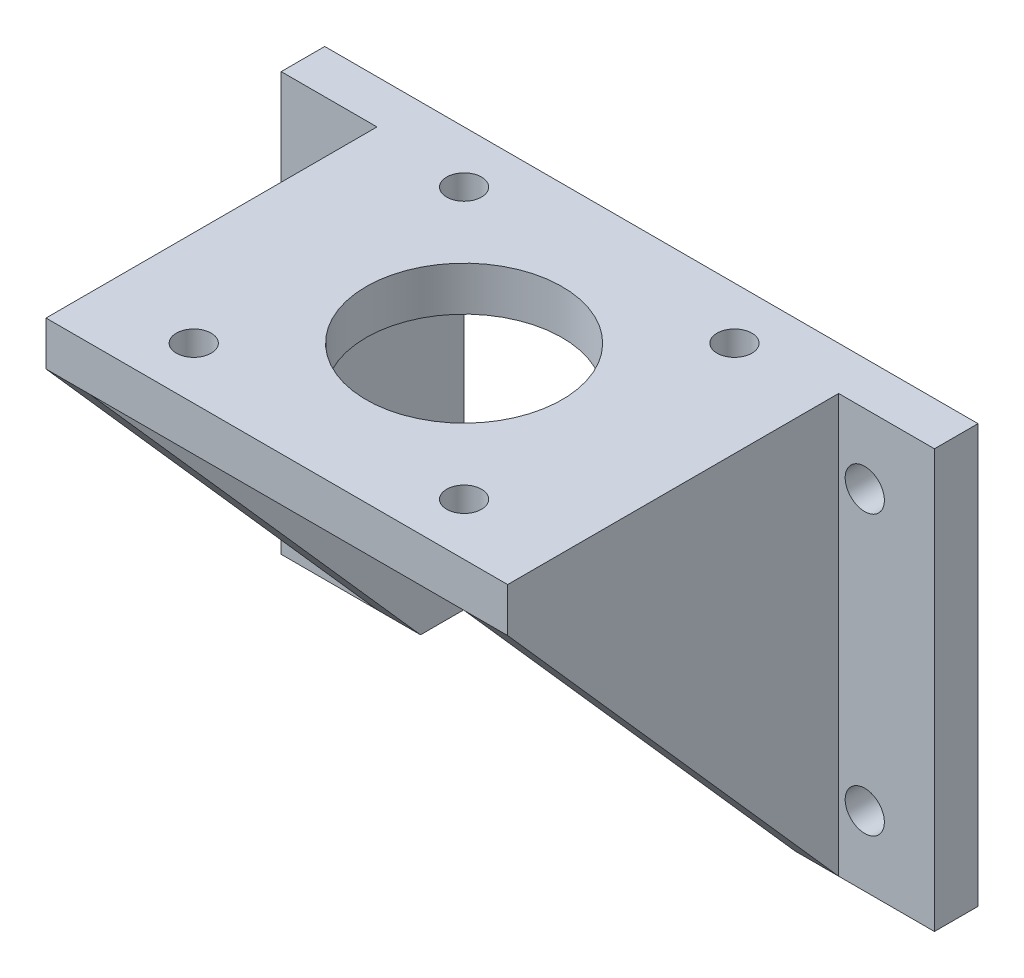
SolidWorks part; units mm, degrees
material "Copper"
ref_plane "Front Plane" through (0, 0, 0) normal (0, 0, 1) x (1, 0, 0)
ref_plane "Top Plane" through (0, 0, 0) normal (0, 1, 0) x (1, 0, 0)
ref_plane "Right Plane" through (0, 0, 0) normal (1, 0, 0) x (0, 0, -1)
sketch "Sketch1" plane through (0, 0, 0) normal (0, 0, 1) x (1, 0, 0)
  line L0 (0, 0) -> (0, 43)
  line L1 (0, 43) -> (43, 43)
  line L2 (43, 43) -> (43, 0)
  line L3 (43, 0) -> (59, 0)
  line L4 (59, 0) -> (59, 48)
  line L5 (59, 48) -> (-16, 48)
  line L6 (-16, 48) -> (-16, 0)
  line L7 (-16, 0) -> (0, 0)
  circle A0 centre (-8, 40) radius 2.25
  circle A1 centre (51, 40) radius 2.25
  circle A2 centre (51, 8) radius 2.25
  circle A3 centre (-8, 8) radius 2.25
  dimension "D5" = 8
  dimension "D1" = 16
  dimension "D2" = 16
  dimension "D3" = 5
  dimension "D4" = 43
  dimension "D6" = 8
  dimension "D7" = 2
  dimension "D8" = 2
extrude "Boss-Extrude1" add sketch "Sketch1" along normal blind 5
sketch "Sketch2" plane through (0, 0, 5) normal (0, 0, 1) x (1, 0, 0)
  line L1 (59, 48) -> (-16, 48) construction
  line L2 (-5, 42.9307) -> (48, 42.9307)
  line L3 (-5, 42.9307) -> (-5, 48)
  line L4 (-5, 48) -> (48, 48)
  line L5 (48, 42.9307) -> (48, 48)
  line L6 (0, 0) -> (0, 43) construction
  line L7 (43, 43) -> (43, 0) construction
  dimension "D1" = 5
  dimension "D2" = 5
extrude "Boss-Extrude2" add sketch "Sketch2" along normal blind 38
ref_plane "Plane1" through (-5, 0, 0) normal (-1, 0, 0) x (0, 0, 1)
sketch "Sketch3" plane through (-5, 0, 0) normal (-1, 0, 0) x (0, 0, 1)
  line L0 (5, 48) -> (5, 0)
  line L1 (43, 48) -> (5, 48) construction
  line L2 (5, 48) -> (5, 42.9307) construction
  line L3 (5, 0) -> (43, 42.9307)
  line L4 (43, 42.9307) -> (43, 48)
  line L5 (43, 48) -> (5, 48)
extrude "Boss-Extrude3" add sketch "Sketch3" against normal blind 5
ref_plane "Plane2" through (48, 0, 0) normal (1, 0, 0) x (0, 0, -1)
sketch "Sketch4" plane through (48, 0, 0) normal (1, 0, 0) x (0, 0, -1)
  line L0 (-43, 48) -> (-43, 42.9307)
  line L1 (-43, 42.9307) -> (-5, 0)
  line L2 (-5, 0) -> (-5, 48)
  line L3 (-5, 48) -> (-43, 48)
extrude "Boss-Extrude4" add sketch "Sketch4" against normal blind 5
sketch "Sketch5" plane through (0, 48, 0) normal (0, 1, 0) x (1, 0, 0)
  line L0 (-5, 20.9) -> (-5, -20.9) construction
  line L1 (48, -20.9) -> (48, 20.9) construction
  line L2 (59, 0) -> (-16, 0) construction
  line L3 (48, -43) -> (-5, -43) construction
  circle A0 centre (21.5, -21.5) radius 11.25
  circle A1 centre (5.98, -5.98) radius 2
  circle A2 centre (37.02, -5.98) radius 2
  circle A3 centre (37.02, -37.02) radius 2
  circle A4 centre (5.98, -37.02) radius 2
  dimension "D1" = 22.5
  dimension "D6" = 15.52
  dimension "D2" = 26.5
  dimension "D3" = 26.5
  dimension "D4" = 21.5
  dimension "D5" = 21.5
  dimension "D7" = 15.52
  dimension "D8" = 2
  dimension "D9" = 2
extrude "Cut-Extrude1" cut sketch "Sketch5" against normal through all
